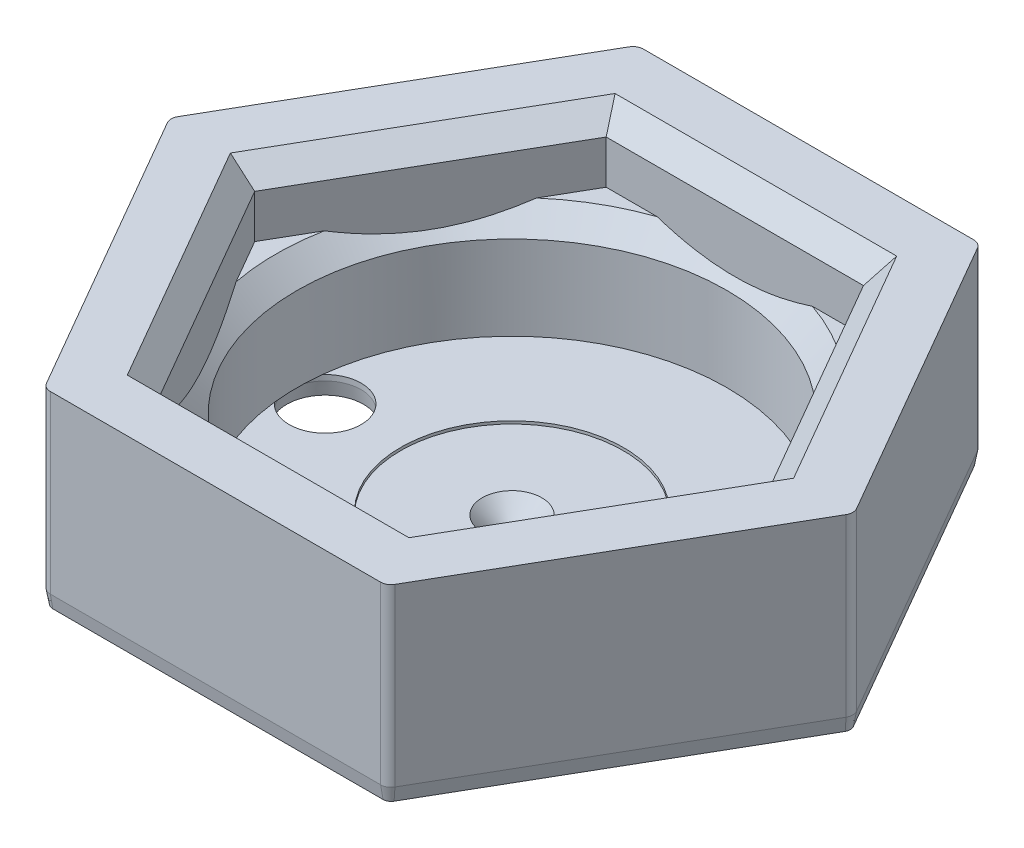
SolidWorks part; units mm, degrees
note: The reader was unsure of these and kept them because the rebuilt part matched: shared geometry of "Sketch1<5>", "Sketch1<6>", "Sketch1<8>", "Sketch1<7>".
ref_plane "Front Plane" through (0, 0, 0) normal (0, 0, 1) x (1, 0, 0)
ref_plane "Top Plane" through (0, 0, 0) normal (0, 1, 0) x (1, 0, 0)
ref_plane "Right Plane" through (0, 0, 0) normal (1, 0, 0) x (0, 0, -1)
sketch "Sketch1" plane through (0, 0, 0) normal (0, 1, 0) x (1, 0, 0)
  line L0 (0, 0) -> (-24.393, 42.25) construction
  line L1 (36.6617, 0) -> (18.3309, 31.75)
  line L2 (18.3309, 31.75) -> (-18.3309, 31.75)
  line L3 (-18.3309, 31.75) -> (-36.6617, 0)
  line L4 (-36.6617, 0) -> (-18.3309, -31.75)
  line L5 (-18.3309, -31.75) -> (18.3309, -31.75)
  line L6 (18.3309, -31.75) -> (36.6617, 0)
  line L7 (48.7861, 0) -> (24.393, 42.25)
  line L8 (24.393, 42.25) -> (-24.393, 42.25)
  line L9 (-24.393, 42.25) -> (-48.7861, 0)
  line L10 (-48.7861, 0) -> (-24.393, -42.25)
  line L11 (-24.393, -42.25) -> (24.393, -42.25)
  line L12 (24.393, -42.25) -> (48.7861, 0)
  line L13 (0, 0) -> (24.393, 42.25) construction
  line L14 (0, 0) -> (48.7861, 0) construction
  line L15 (0, 0) -> (0, 42.25) construction
  circle A0 centre (0, 0) radius 31.75 construction
  circle A1 centre (0, 0) radius 42.25 construction
  circle A4 centre (26.625, 0) radius 5.125
  circle A5 centre (0, 0) radius 15.875
  circle A6 centre (0, 0) radius 30.625
  circle A10 centre (-26.625, 0) radius 5.125
  circle A13 centre (0, 0) radius 1.25
  dimension "D1" = 10.5
  dimension "D2" = 31.75
  dimension "D3" = 10.25
  dimension "D6" = 61.25
  dimension "D9" = 2.5
  dimension "D5" = 63.5
  dimension "D8" = 2
extrude "Boss-Extrude1" add sketch "Sketch1" along normal blind 27 contours L14 L6 L5 L4 L3 L0 L9 L10 L11 L12 | L2 L13 L8 L0 | L1 L14 L7 L13
extrude "Boss-Extrude2" add sketch "Sketch1<5>" along normal blind 2.8
sketch "Sketch1<5>" plane through (0, 0, 0) normal (0, 1, 0) x (1, 0, 0) same geometry as "Sketch1"
extrude "Boss-Extrude3" add sketch "Sketch1<6>" along normal blind 15 from surface
sketch "Sketch1<6>" plane through (0, 0, 0) normal (0, 1, 0) x (1, 0, 0) same geometry as "Sketch1"
extrude "Cut-Extrude2" cut sketch "Sketch1<8>" against normal blind 10 from surface at 2.8 contours A6 A10 | A6 A10 | A4 A6 | A6 A4
sketch "Sketch1<8>" plane through (0, 0, 0) normal (0, 1, 0) x (1, 0, 0) same geometry as "Sketch1"
extrude "Cut-Extrude1" cut sketch "Sketch1<7>" against normal blind 0.4 from surface at 2.8 contours A5 starting at face at (0, 2.8, 0)
sketch "Sketch1<7>" plane through (0, 0, 0) normal (0, 1, 0) x (1, 0, 0) same geometry as "Sketch1"
chamfer "Chamfer1" distance 3 angle 45 7 edges at (0, 17.8, 30.625) (27.4963, 27, 15.875) (0, 27, 31.75) (-27.4963, 27, 15.875) (-27.4963, 27, -15.875) (27.4963, 27, -15.875) (0, 27, -31.75)
fillet "Fillet1" radius 1.5 6 edges at (24.393, 13.5, -42.25) (-24.393, 13.5, -42.25) (48.7861, 13.5, 0) (24.393, 13.5, 42.25) (-24.393, 13.5, 42.25) (-48.7861, 13.5, 0)
chamfer "Chamfer2" distance 3 angle 45 1 edges at (0, 2.4, 1.25)
chamfer "Chamfer3" distance 2 angle 10 2 edges at (26.625, 0, 5.125) (-26.625, 0, 5.125)
chamfer "Chamfer4" distance 2 angle 10 12 edges at (36.5896, 0, -21.125) (0, 0, -42.25) (-36.5896, 0, -21.125) (-36.5896, 0, 21.125) (0, 0, 42.25) (36.5896, 0, 21.125) (-48.554, 0, 0) (-24.277, 0, -42.049) (-24.277, 0, 42.049) (24.277, 0, -42.049) (24.277, 0, 42.049) (48.554, 0, 0)
